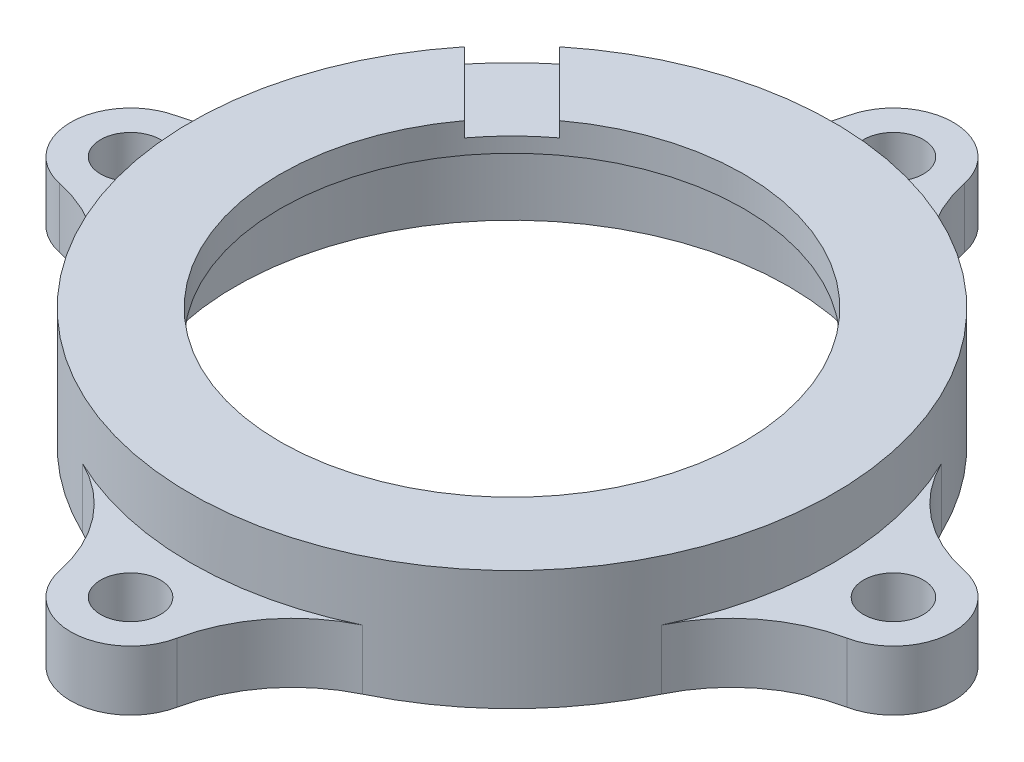
SolidWorks part; units mm, degrees
ref_plane "Front Plane" through (0, 0, 0) normal (0, 0, 1) x (1, 0, 0)
ref_plane "Top Plane" through (0, 0, 0) normal (0, 1, 0) x (1, 0, 0)
ref_plane "Right Plane" through (0, 0, 0) normal (1, 0, 0) x (0, 0, -1)
sketch "Sketch1" plane through (0, 0, 0) normal (0, 1, 0) x (1, 0, 0)
  circle A0 centre (0, 0) radius 21.5
  circle A1 centre (0, 0) radius 15.5
  dimension "D1" = 43
  dimension "D2" = 31
extrude "Boss-Extrude1" add sketch "Sketch1" along normal blind 4
sketch "Sketch2" plane through (0, 0, 0) normal (0, -1, 0) x (1, 0, 0)
  circle A0 centre (0, 0) radius 18.5
  circle A1 centre (0, 0) radius 21.5
  dimension "D1" = 37
extrude "Boss-Extrude2" add sketch "Sketch2" along normal blind 4
sketch "Sketch3" plane through (0, 0, 0) normal (0, -1, 0) x (1, 0, 0)
  circle A0 centre (0, 0) radius 15
  circle A1 centre (0, 0) radius 18.5
extrude "Cut-Extrude1" cut sketch "Sketch3" against normal blind 2
sketch "Sketch4" plane through (0, -4, 0) normal (0, -1, 0) x (1, 0, 0)
  line L0 (-25.5, 4) -> (-20.187, 4)
  line L1 (-20.187, 4) -> (-20.187, -4)
  line L2 (-20.187, -4) -> (-25.5, -4)
  line L3 (4, 20.187) -> (-4, 20.187)
  line L4 (-4, 20.187) -> (-4, 25.5)
  line L5 (4, 25.5) -> (4, 20.187)
  line L6 (20.187, -4) -> (20.187, 4)
  line L7 (20.187, 4) -> (25.5, 4)
  line L8 (25.5, -4) -> (20.187, -4)
  line L9 (-4, -20.187) -> (4, -20.187)
  line L10 (4, -20.187) -> (4, -25.5)
  line L11 (-4, -25.5) -> (-4, -20.187)
  circle A0 centre (0, 0) radius 25.5 construction
  circle A1 centre (-25.5, 0) radius 2
  arc A2 (-25.5, 4) -> (-25.5, -4) centre (-25.5, 0) ccw
  circle A4 centre (0, 25.5) radius 2
  arc A5 (4, 25.5) -> (-4, 25.5) centre (0, 25.5) ccw
  circle A6 centre (25.5, 0) radius 2
  arc A7 (25.5, -4) -> (25.5, 4) centre (25.5, 0) ccw
  circle A8 centre (0, -25.5) radius 2
  arc A9 (-4, -25.5) -> (4, -25.5) centre (0, -25.5) ccw
  circle A10 centre (0, 0) radius 21.5 construction
  point P32 (0, 0)
  dimension "D1" = 4
  dimension "D2" = 2
  dimension "D3" = 4
extrude "Boss-Extrude3" add sketch "Sketch4" against normal blind 4
fillet "Fillet1" radius 10 8 edges at (-4, -2, 21.1246) (4, -2, -21.1246) (-21.1246, -2, -4) (-21.1246, -2, 4) (-4, -2, -21.1246) (21.1246, -2, -4) (21.1246, -2, 4) (4, -2, 21.1246)
sketch "Sketch5" plane through (0, 4, 0) normal (0, 1, 0) x (1, 0, 0)
  circle A0 centre (0, 0) radius 29.5
  circle A1 centre (0, 0) radius 31.5
  dimension "D1" = 59
  dimension "D2" = 2
extrude "Cut-Extrude2" [suppressed] cut sketch "Sketch5" against normal through all
sketch "Sketch6" plane through (0, 4, 0) normal (0, 1, 0) x (1, 0, 0)
  line L0 (0, 0) -> (8.1989, 0) construction
  line L1 (0, 0) -> (-10.2583, 10.2583) construction
  line L2 (-10.9602, 10.9602) -> (-15.2028, 15.2028) construction
  line L3 (-8.6673, 11.8492) -> (-15.1906, 18.3726)
  line L4 (-8.6673, 11.8492) -> (-11.8492, 8.6673)
  line L5 (-15.1906, 18.3726) -> (-18.3726, 15.1906)
  line L6 (-11.8492, 8.6673) -> (-18.3726, 15.1906)
  line L7 (-8.6673, 11.8492) -> (-18.3726, 15.1906) construction
  line L8 (-15.1906, 18.3726) -> (-11.8492, 8.6673) construction
  point P5 (0, 0)
  point P6 (-13.8794, 13.6437)
  point P8 (0, 0)
  point P13 (-10.2583, 10.2583)
  dimension "D1" = 135
  dimension "D2" = 4.5
extrude "Cut-Extrude3" cut sketch "Sketch6" against normal blind 1
sketch "Sketch7" plane through (0, 3, 0) normal (0, 1, 0) x (1, 0, 0)
  line L0 (-14.5727, 11.3907) -> (-11.3907, 14.5727) construction
  line L1 (-16.7103, 13.5283) -> (-12.4351, 9.2531) construction
  line L2 (-9.2531, 12.4351) -> (-13.5283, 16.7103) construction
  point P0 (-12.9817, 12.9817)
